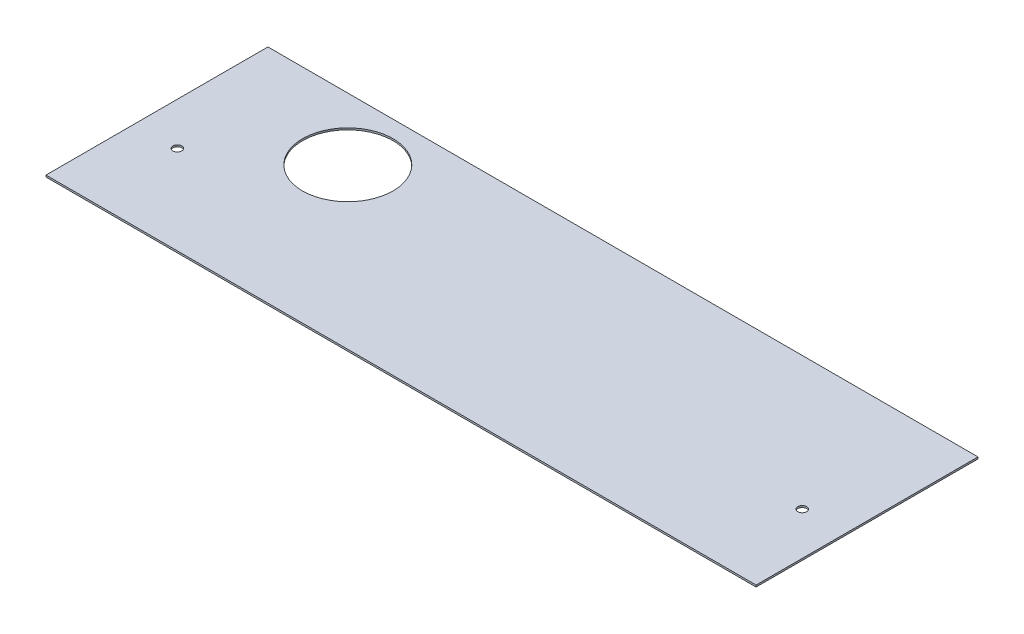
SolidWorks part; units mm, degrees
material "1060 Сплав"
ref_plane "Front" through (0, 0, 0) normal (0, 0, 1) x (1, 0, 0)
ref_plane "Top" through (0, 0, 0) normal (0, 1, 0) x (1, 0, 0)
ref_plane "Right" through (0, 0, 0) normal (1, 0, 0) x (0, 0, -1)
sketch "Эскиз2" plane through (0, 0, 0) normal (0, 1, 0) x (1, 0, 0)
  line L0 (200, 0) -> (200, 83.8274) construction
  line L1 (0, 0) -> (400, 0)
  line L2 (0, 0) -> (0, 125)
  line L3 (0, 125) -> (400, 125)
  line L4 (400, 0) -> (400, 125)
  circle A0 centre (24, 50) radius 2.5
  circle A1 centre (376, 50) radius 2.5
  dimension "D3" = 5
  dimension "D4" = 176
  dimension "D5" = 50
  dimension "D1" = 125
  dimension "D2" = 400
base flange "Базовая кромка1" sketch "Эскиз2" thickness 1 reverse thickness direction no parameters "D1"=1.5
sketch "Эскиз3" plane through (0, 0, 0) normal (0, 1, 0) x (1, 0, 0)
  line L0 (0, 125) -> (0, 0) construction
  line L1 (400, 125) -> (0, 125) construction
  circle A0 centre (80, 90) radius 25.5
  dimension "D3" = 51
  dimension "D1" = 80
  dimension "D2" = 35
extrude "Вырез-Вытянуть1" cut sketch "Эскиз3" against normal through all normal cut yes
sketch "Сгиб-Линии1" [suppressed] plane through (0, 0, 0) normal (0, 1, 0) x (1, 0, 0)
sketch "Граничная рамка1" [suppressed] plane through (0, 0, 0) normal (0, 1, 0) x (1, 0, 0)
sheet metal parameters "Листовой металл1" thickness 1 parameters "D1"=1.5
flat pattern "Развертка1" [suppressed]
sketch "Сгиб-Линии2" plane through (0, 0, 0) normal (0, 1, 0) x (1, 0, 0)
sketch3d "Граничная рамка2" [suppressed]
  line L0 (400, 125, 0) -> (0, 125, 0) construction
  line L1 (400, 0, 0) -> (0, 0, 0) construction
  line L2 (400, 125, 0) -> (400, 0, 0) construction
  line L3 (0, 125, 0) -> (0, 0, 0) construction
sheet metal parameters "Листовой металл3" thickness 1 parameters "D1"=1.5
flat pattern "Развертка1"
sketch "Сгиб-Линии2" plane through (0, 0, 0) normal (0, 1, 0) x (1, 0, 0)
sketch3d "Граничная рамка2" [suppressed]
  line L0 (400, 125, 0) -> (0, 125, 0) construction
  line L1 (400, 0, 0) -> (0, 0, 0) construction
  line L2 (400, 125, 0) -> (400, 0, 0) construction
  line L3 (0, 125, 0) -> (0, 0, 0) construction
